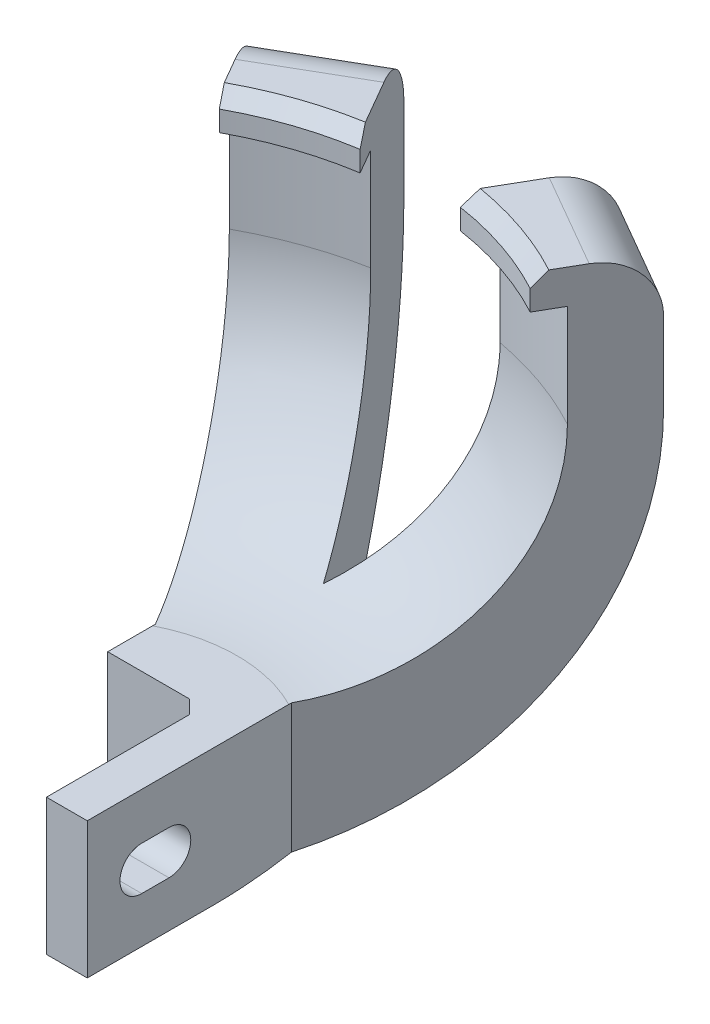
SolidWorks part; units mm, degrees
ref_plane "Plan de face" through (0, 0, 0) normal (0, 0, 1) x (1, 0, 0)
ref_plane "Plan de dessus" through (0, 0, 0) normal (0, 1, 0) x (1, 0, 0)
ref_plane "Plan de droite" through (0, 0, 0) normal (1, 0, 0) x (0, 0, -1)
sketch "Esquisse2" plane through (0, 0, 0) normal (0, 1, 0) x (1, 0, 0)
  line L0 (-5, 7.5) -> (-15, 24.8205)
  line L1 (5, -7.5) -> (-5, -7.5)
  line L2 (5, -7.5) -> (5, 7.5)
  line L4 (-5, -7.5) -> (-5, 7.5)
  line L5 (5, -7.5) -> (-5, 7.5) construction
  line L6 (5, 7.5) -> (-5, -7.5) construction
  line L7 (-15, 24.8205) -> (-8.0718, 28.8205)
  line L8 (-8.0718, 28.8205) -> (0, 14.8397)
  line L9 (0, 14.8397) -> (8.0718, 28.8205)
  line L10 (8.0718, 28.8205) -> (15, 24.8205)
  line L11 (15, 24.8205) -> (5, 7.5)
  point P0 (0, 0)
  dimension "D1" = 150
  dimension "D2" = 15
  dimension "D3" = 150
  dimension "D4" = 60
  dimension "D5" = 8
  dimension "D6" = 10
  dimension "D7" = 20
  dimension "D8" = 20
  dimension "D9" = 5
  dimension "D10" = 8
extrude "Boss.-Extru.1" add sketch "Esquisse2" along normal blind 35
sketch "Esquisse3" plane through (0, 35, 0) normal (0, 1, 0) x (1, 0, 0)
  line L0 (-5, -7.5) -> (5, -7.5) construction
  circle A0 centre (0, -2.5) radius 26
  dimension "D2" = 52
  dimension "D1" = 5
extrude "Enlèv. mat.-Extru.1" cut sketch "Esquisse3" against normal blind 25
fillet "Congé1" radius 15 1 edges at (-8.6886, 10, -22.0053)
fillet "Congé2" radius 25 2 edges at (-11.5359, 0, -26.8205) (11.5359, 0, -26.8205)
sketch "Esquisse4" plane through (0, 10, 0) normal (0, 1, 0) x (1, 0, 0)
  line L1 (-5, -7.5) -> (2, -7.5)
  line L2 (-5, -7.5) -> (-5, 4)
  line L3 (-5, 4) -> (2, 4)
  line L4 (2, -7.5) -> (2, 4)
  dimension "D1" = 11.5
  dimension "D2" = 7
extrude "Enlèv. mat.-Extru.2" cut sketch "Esquisse4" against normal blind 25
sketch "Esquisse5" plane through (2, 0, 0) normal (-1, 0, 0) x (0, 0, 1)
  line L0 (1.5, 4.9717) -> (3.5, 4.9717) construction
  line L1 (1.5, 6.5717) -> (3.5, 6.5717)
  line L2 (1.5, 3.3717) -> (3.5, 3.3717)
  line L3 (7.5, 0) -> (7.5, 10) construction
  arc A0 (1.5, 6.5717) -> (1.5, 3.3717) centre (1.5, 4.9717) ccw
  arc A1 (3.5, 3.3717) -> (3.5, 6.5717) centre (3.5, 4.9717) ccw
  point P2 (2.5, 4.9717)
  dimension "D1" = 3.2
  dimension "D2" = 2
  dimension "D3" = 5
extrude "Enlèv. mat.-Extru.3" cut sketch "Esquisse5" against normal through all
sketch "Esquisse6" plane through (0, 35, 0) normal (0, 1, 0) x (1, 0, 0)
  line L0 (-15, 24.8205) -> (-8.0718, 28.8205)
  line L1 (-15, 24.8205) -> (-9, 14.4282)
  line L2 (-8.0718, 28.8205) -> (-2.0718, 18.4282)
  line L3 (-9, 14.4282) -> (-2.0718, 18.4282)
  line L4 (8.0718, 28.8205) -> (15, 24.8205)
  line L5 (8.0718, 28.8205) -> (2.0718, 18.4282)
  line L6 (15, 24.8205) -> (9, 14.4282)
  line L7 (2.0718, 18.4282) -> (9, 14.4282)
  dimension "D1" = 12
  dimension "D2" = 12
extrude "Boss.-Extru.2" add sketch "Esquisse6" against normal blind 2.5
sketch "Esquisse7" plane through (0, 35, 0) normal (0, 1, 0) x (1, 0, 0)
  circle A0 centre (0, -2.5) radius 24
  dimension "D1" = 48
extrude "Enlèv. mat.-Extru.4" cut sketch "Esquisse7" against normal blind 3
chamfer "Chanfrein1" distance 1 angle 45 1 edges at (-7.6598, 35, -20.2448)
fillet "Congé4" radius 4 2 edges at (11.5359, 35, -26.8205) (-11.5359, 35, -26.8205)
chamfer "Chanfrein2" distance 1 angle 45 1 edges at (2, 5.0022, -4)
